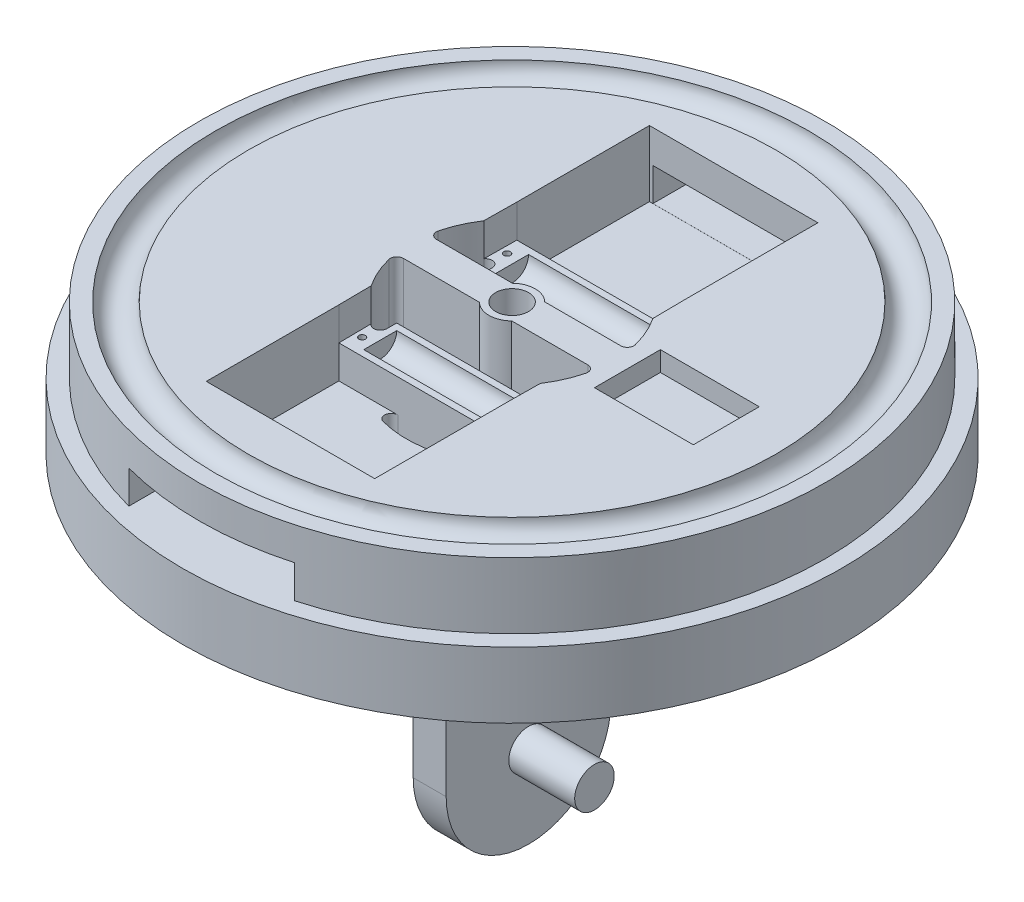
SolidWorks part; units mm, degrees
ref_plane "Front Plane" through (0, 0, 0) normal (0, 0, 1) x (1, 0, 0)
ref_plane "Top Plane" through (0, 0, 0) normal (0, 1, 0) x (1, 0, 0)
ref_plane "Right Plane" through (0, 0, 0) normal (1, 0, 0) x (0, 0, -1)
sketch "Sketch1" plane through (0, 0, 0) normal (0, 1, 0) x (1, 0, 0)
  circle A0 centre (0, 0) radius 50
  dimension "Outer Diameter" = 100
extrude "Boss-Extrude1" add sketch "Sketch1" along normal blind 10
sketch "Sketch3" plane through (0, 10, 0) normal (0, 1, 0) x (1, 0, 0)
  circle A0 centre (0, 0) radius 47.5
  dimension "Lip outer diameter" = 95
extrude "Boss-Extrude2" add sketch "Sketch3" along normal blind 10
sketch "Sketch4" plane through (0, 20, 0) normal (0, 1, 0) x (1, 0, 0)
  circle A2 centre (0, 0) radius 42.5
  circle A3 centre (0, 0) radius 42.5
  dimension "Bearing Path" = 5
sketch "Sketch5" plane through (0, 0, 0) normal (0, 0, 1) x (1, 0, 0)
  line L0 (0, 0) -> (0, 20) construction
  line L1 (42.5, 20) -> (-42.5, 20) construction
  line L2 (0, 20) -> (42.5, 20) construction
  line L3 (47.5, 20) -> (-47.5, 20) construction
  circle A0 centre (42.5, 20) radius 2.5
  dimension "D2" = 5
  dimension "D1" = 42.5
sweep "Cut-Sweep1" cut profiles "Sketch5" path "Sketch4"
sketch "Sketch6" plane through (0, 20, 0) normal (0, 1, 0) x (1, 0, 0)
  line L0 (0, -55.8694) -> (0, 58.2655) construction
  line L1 (60.5463, 0) -> (-59.0949, 0) construction
  circle A0 centre (0, 0) radius 2.5
  dimension "Heated Screw Insert Outer Diameter" = 5
extrude "Cut-Extrude1" cut sketch "Sketch6" against normal blind 5
sketch "Sketch7" plane through (0, 20, 0) normal (0, 1, 0) x (1, 0, 0)
  circle A0 centre (0, 0) radius 47.5 construction
  circle A1 centre (0, 0) radius 47.5
extrude "Cut-Extrude2" cut sketch "Sketch7" against normal blind 0.01
ref_plane "Plane1" through (0, 14.99, 0) normal (0, 1, 0) x (1, 0, 0)
sketch "Sketch9" plane through (0, 14.99, 0) normal (0, 1, 0) x (1, 0, 0)
  line L0 (0, 0) -> (0, 10) construction
  line L1 (0, 0) -> (0, -10) construction
  dimension "D1" = 10
sketch "Sketch10" plane through (0, 0, 0) normal (1, 0, 0) x (0, 0, -1)
  line L2 (0, 14.99) -> (10, 14.99) construction
  circle A0 centre (-10, 14.99) radius 2.5
  circle A1 centre (10, 14.99) radius 2.5
  dimension "Center Rod OD" = 5
extrude "Cut-Extrude4" cut sketch "Sketch10" against normal mid plane 20
sketch "Sketch11" plane through (0, 19.99, 0) normal (0, 1, 0) x (1, 0, 0)
  line L0 (-23.8788, 0) -> (22.8567, 0) construction
  line L1 (2.4495, 2.5) -> (22.4495, 2.5)
  line L18 (-11, 6.5) -> (11, 6.5)
  line L19 (11, 13.5) -> (11, 6.5)
  line L20 (11, 13.5) -> (-11, 13.5)
  line L21 (-11, 6.5) -> (-11, 13.5)
  line L22 (11, -6.5) -> (-11, -6.5)
  line L23 (-11, -13.5) -> (-11, -6.5)
  line L24 (-11, -13.5) -> (11, -13.5)
  line L25 (11, -13.5) -> (11, -6.5)
  line L26 (2.4495, -2.5) -> (22.4495, -2.5)
  line L27 (22.4495, -2.5) -> (22.4495, 2.5)
  line L28 (0, -18.9126) -> (0, 28.1361) construction
  line L29 (-2.4495, 2.5) -> (-22.4495, 2.5)
  line L30 (-22.4495, -2.5) -> (-22.4495, 2.5)
  line L31 (-2.4495, -2.5) -> (-22.4495, -2.5)
  circle A0 centre (0, 0) radius 2.5 construction
  circle A1 centre (0, 0) radius 2.5
  circle A2 centre (0, 0) radius 3.5
  circle A3 centre (0, 0) radius 17.4141 construction
  arc A4 (-11, 10.7979) -> (-11, -10.7979) centre (0, 0) ccw
  circle A6 centre (0, 0) radius 15.4141 construction
  arc A7 (11, -10.7979) -> (11, 10.7979) centre (0, 0) ccw
  arc A8 (8.5878, -13.5) -> (-8.5878, -13.5) centre (0, 0) cw
  arc A9 (-8.5878, 13.5) -> (8.5878, 13.5) centre (0, 0) cw
  point P24 (15.4141, 0)
  dimension "D4" = 2
  dimension "D7" = 16
  dimension "D5" = 5
  dimension "D6" = 20
  dimension "D2" = 1
extrude "Cut-Extrude7" cut sketch "Sketch11" against normal through all contours A8 L24 | L25 A7 L26 A2 L31 A4 L23 L22 | L1 A7 L19 L18 L21 A4 L29 A2 | A9 L20 region at (0, 19.99, -4.909) region at (0, 19.99, 4.909) region at (0, 19.99, -14.507) region at (0, 19.99, 14.507)
sketch "Sketch18" plane through (0, 19.99, 0) normal (0, 1, 0) x (1, 0, 0)
  line L0 (11, 10.7979) -> (11, 6.5) construction
  line L1 (-10, -7.5) -> (10, -7.5)
  line L2 (-10, -7.5) -> (-10, -12.5)
  line L3 (-10, -12.5) -> (10, -12.5)
  line L4 (10, -7.5) -> (10, -12.5)
  line L5 (-10, -7.5) -> (10, -12.5) construction
  line L6 (-10, -12.5) -> (10, -7.5) construction
  line L7 (-10, 12.5) -> (10, 12.5)
  line L8 (-10, 12.5) -> (-10, 7.5)
  line L9 (-10, 7.5) -> (10, 7.5)
  line L10 (10, 12.5) -> (10, 7.5)
  line L11 (-10, 12.5) -> (10, 7.5) construction
  line L12 (-10, 7.5) -> (10, 12.5) construction
  line L13 (-11, 6.5) -> (-11, 10.7979) construction
  line L14 (-11, 6.5) -> (11, 6.5) construction
  line L15 (8.5878, 13.5) -> (-8.5878, 13.5) construction
  line L16 (11, 10.7979) -> (11, 6.5)
  line L17 (-11, 6.5) -> (-11, 10.7979)
  line L18 (-11, 6.5) -> (11, 6.5)
  line L19 (8.5878, 13.5) -> (-8.5878, 13.5)
  point P0 (0, -10)
  point P6 (0, 10)
  dimension "D1" = 1
  dimension "D2" = 1
extrude "Cut-Extrude11" cut sketch "Sketch18" against normal blind 5 contours L4 L1 L2 L3 | L10 L7 L8 L9 region at (0, 19.99, 10) region at (0, 19.99, -10)
fillet "Fillet1" radius 1 8 edges at (15.21, 9.995, -2.5) (-15.21, 9.995, -2.5) (-15.21, 9.995, 2.5) (-11, 9.995, -10.7979) (11, 9.995, -10.7979) (15.21, 9.995, 2.5) (11, 9.995, 10.7979) (-11, 9.995, 10.7979)
fillet "Fillet2" radius 1 4 edges at (-8.5878, 9.995, -13.5) (8.5878, 9.995, -13.5) (8.5878, 9.995, 13.5) (-8.5878, 9.995, 13.5)
sketch "Sketch13" plane through (0, 0, 0) normal (1, 0, 0) x (0, 0, -1)
  line L0 (0, 27.6366) -> (0, -53.6815) construction
  line L1 (-12.5, 0) -> (12.5, 0)
  line L2 (-50, 0) -> (50, 0) construction
  line L3 (-12.5, 0) -> (-12.5, -37.5)
  line L4 (12.5, 0) -> (12.5, -37.5)
  arc A0 (-12.5, -37.5) -> (12.5, -37.5) centre (0, -37.5) ccw
  point P13 (0, 0)
  point P14 (0, -50)
  dimension "D2" = 50
  dimension "D1" = 12.5
extrude "Boss-Extrude3" add sketch "Sketch13" along normal mid plane 5
sketch "Sketch14" plane through (2.5, 0, 0) normal (1, 0, 0) x (0, 0, -1)
  line L0 (-6, -37.5) -> (6, -37.5) construction
  line L1 (6, -32.5) -> (6, -42.5) construction
  line L2 (7.5, -32.5) -> (7.5, -42.5)
  line L3 (4.5, -32.5) -> (4.5, -42.5)
  line L4 (0, -30.6025) -> (0, -6.6194) construction
  line L5 (-6, -32.5) -> (-6, -42.5) construction
  line L6 (-7.5, -32.5) -> (-7.5, -42.5)
  line L7 (-4.5, -32.5) -> (-4.5, -42.5)
  arc A0 (-12.5, -37.5) -> (12.5, -37.5) centre (0, -37.5) ccw construction
  arc A1 (-12.5, -37.5) -> (12.5, -37.5) centre (0, -37.5) ccw
  circle A2 centre (0, -37.5) radius 3
  arc A3 (7.5, -32.5) -> (4.5, -32.5) centre (6, -32.5) ccw
  arc A4 (4.5, -42.5) -> (7.5, -42.5) centre (6, -42.5) ccw
  arc A5 (-7.5, -32.5) -> (-4.5, -32.5) centre (-6, -32.5) cw
  arc A6 (-4.5, -42.5) -> (-7.5, -42.5) centre (-6, -42.5) cw
  point P8 (6, -37.5)
  point P18 (-6, -37.5)
  dimension "Bushing ID" = 6
  dimension "D2" = 12
  dimension "D3" = 10
  dimension "Belt track Bolt Diameter" = 3
fillet "Fillet3" radius 1 2 edges at (0, 0, -12.5) (0, 0, 12.5)
extrude "Boss-Extrude5" add sketch "Sketch14" along normal blind 10 contours A2 region at (2.5, -37.5, 0)
mirror "Mirror2" about plane through (0, 0, 0) normal (1, 0, 0) of "Boss-Extrude5"
sketch "Sketch15" plane through (0, 19.99, 0) normal (0, 1, 0) x (1, 0, 0)
  line L0 (0, 0) -> (32.5, 0) construction
  line L1 (17.5, 5) -> (32.5, 5)
  line L2 (17.5, 5) -> (17.5, -5)
  line L3 (17.5, -5) -> (32.5, -5)
  line L4 (32.5, 5) -> (32.5, -5)
  circle A0 centre (0, 0) radius 15 construction
  circle A1 centre (0, 0) radius 22 construction
  dimension "D1" = 30
  dimension "D3" = 15
  dimension "D4" = 17.5
  dimension "D5" = 10
  dimension "D2" = 7
extrude "Cut-Extrude8" cut sketch "Sketch15" against normal blind 3
sketch "Sketch16" plane through (0, 19.99, 0) normal (0, 1, 0) x (1, 0, 0)
  line L0 (-59.8893, 0) -> (63.5411, 0) construction
  line L1 (-12.7778, -13.5) -> (12.7778, -13.5)
  line L2 (-12.7778, -13.5) -> (-12.7778, -33.6172)
  line L3 (-12.7778, -33.6172) -> (12.7778, -33.6172)
  line L4 (12.7778, -13.5) -> (12.7778, -33.6172)
  line L5 (-12.7778, -13.5) -> (12.7778, -33.6172) construction
  line L6 (-12.7778, -33.6172) -> (12.7778, -13.5) construction
  line L7 (-3.8406, -13.5) -> (3.8406, -13.5) construction
  point P0 (0, -23.5586)
extrude "Cut-Extrude9" cut sketch "Sketch16" against normal blind 10 contours L2 L1 L4 L3
sketch "Sketch17" plane through (0, 0, 13.5) normal (0, 0, 1) x (1, 0, 0)
  line L0 (50, 10) -> (-50, 10) construction
  line L1 (-12.2453, 15) -> (12.7547, 15)
  line L2 (-12.2453, 15) -> (-12.2453, 10)
  line L3 (-12.2453, 10) -> (12.7547, 10)
  line L4 (12.7547, 15) -> (12.7547, 10)
  line L5 (-12.2453, 15) -> (12.7547, 10) construction
  line L6 (-12.2453, 10) -> (12.7547, 15) construction
  point P0 (0.2547, 12.5)
  dimension "D1" = 5
  dimension "D2" = 25
extrude "Cut-Extrude10" cut sketch "Sketch17" along normal through all
mirror "Mirror3" about plane through (0, 0, 0) normal (0, 0, 1) of "Cut-Extrude10", "Cut-Extrude9"
sketch "Sketch20" plane through (0, 19.99, 0) normal (0, 1, 0) x (1, 0, 0)
  line L0 (-12.7778, -13.5) -> (-3.8406, -13.5) construction
  line L1 (-11, -6.5) -> (11, -6.5)
  line L2 (-11, -6.5) -> (-11, -13.5)
  line L3 (-11, -13.5) -> (11, -13.5)
  line L4 (11, -6.5) -> (11, -13.5)
  line L5 (11, -7.9853) -> (11, -6.5) construction
  line L6 (11, -7.9853) -> (11, -6.5)
  line L7 (-38.4945, 0) -> (38.4945, 0) construction
  line L8 (-11, 13.5) -> (11, 13.5)
  line L9 (11, 6.5) -> (11, 13.5)
  line L10 (-11, 6.5) -> (11, 6.5)
  line L11 (-11, 6.5) -> (-11, 13.5)
  line M6 (-10, -7.5) -> (10, -7.5)
  line M7 (10, -7.5) -> (10, -12.5)
  line M8 (10, -12.5) -> (-10, -12.5)
  line M9 (-10, -12.5) -> (-10, -7.5)
  line M10 (-10, 12.5) -> (10, 12.5)
  line M11 (10, 12.5) -> (10, 7.5)
  line M12 (10, 7.5) -> (-10, 7.5)
  line M13 (-10, 7.5) -> (-10, 12.5)
  line M16 (11, -7.9853) -> (11, -6.5)
  line M17 (11, -6.5) -> (-11, -6.5)
  line M18 (-11, -6.5) -> (-11, -7.9853)
  line M34 (-11, 7.9853) -> (-11, 6.5)
  line M35 (-11, 6.5) -> (11, 6.5)
  line M36 (11, 6.5) -> (11, 7.9853)
  line M46 (-12.7778, -13.5) -> (12.7778, -13.5)
  line M51 (12.7778, 13.5) -> (-12.7778, 13.5)
extrude "Cut-Extrude13" cut sketch "Sketch20" against normal blind 5 contours L4 L2 M16 M17 M18 M46 M9 M6 M7 M8 | L11 L9 M34 M35 M36 M51 M13 M10 M11 M12 region at (0, 19.99, 6.7309) region at (0, 19.99, -13.2691)
sketch "Sketch21" plane through (0, 19.99, 0) normal (0, 1, 0) x (1, 0, 0)
  line L0 (11, -13.5) -> (12.7778, -13.5) construction
  line L1 (11, -7.9853) -> (11, -13.5) construction
  line L2 (11, -13.5) -> (12.7778, -13.5)
  line L3 (11, -7.9853) -> (11, -13.5)
  line L4 (-12.7778, -13.5) -> (-11, -13.5) construction
  line L5 (-11, -7.9853) -> (-11, -13.5) construction
  line L6 (-12.7778, -13.5) -> (-11, -13.5)
  line L7 (-11, -7.9853) -> (-11, -13.5)
  line L8 (-12.8325, -8.5393) -> (-12.7778, -13.5)
  line L9 (12.8325, -8.5393) -> (12.7778, -13.5)
  arc A0 (11, -7.9853) -> (12.8325, -8.5393) centre (12, -7.9853) ccw construction
  arc A1 (11, -7.9853) -> (12.8325, -8.5393) centre (12, -7.9853) ccw
  arc A2 (-12.8325, -8.5393) -> (-11, -7.9853) centre (-12, -7.9853) ccw construction
  arc A3 (-12.8325, -8.5393) -> (-11, -7.9853) centre (-12, -7.9853) ccw
extrude "Cut-Extrude14" cut sketch "Sketch21" against normal blind 5
mirror "Mirror4" about plane through (0, 0, 0) normal (0, 0, 1) of "Cut-Extrude14"
sketch "Sketch22" plane through (0, 14.99, 0) normal (0, 1, 0) x (1, 0, 0)
  line L0 (-11.75, -11) -> (-11, -11) construction
  line L2 (-21.5824, 0) -> (23.011, 0) construction
  line L3 (0, 0) -> (0, -15.0734) construction
  line L7 (-11, -6.5) -> (-11, -13.5) construction
  line L8 (-12.7778, -13.5) -> (12.7778, -13.5) construction
  line L9 (-11, -7.9853) -> (-11, -13.5) construction
  circle A0 centre (-11.75, -11) radius 0.5
  circle A1 centre (11.75, -11) radius 0.5
  circle A2 centre (-11.75, 11) radius 0.5
  circle A3 centre (11.75, 11) radius 0.5
  point P2 (0, 0)
  dimension "D1" = 0.75
  dimension "D2" = 2.5
  dimension "D4" = 1
extrude "Cut-Extrude15" cut sketch "Sketch22" against normal blind 5
